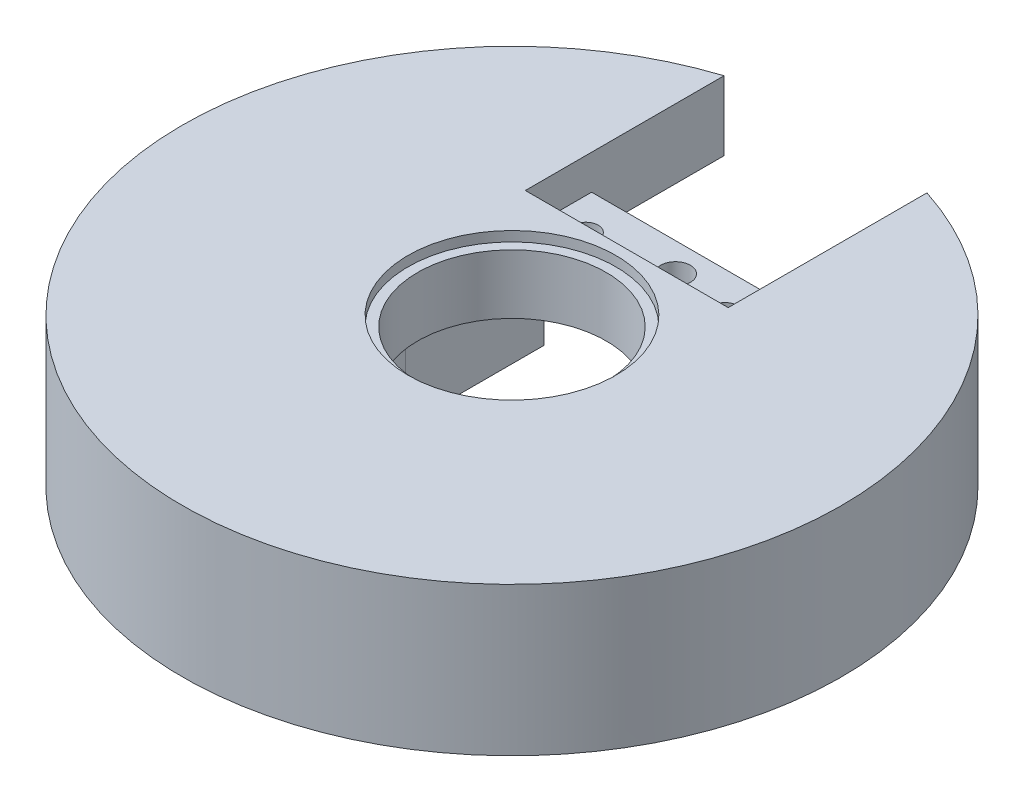
SolidWorks part; units mm, degrees
other "Markup2"
sketch "Sketch11" plane through (-33.3, 0, -31.6832) normal (-0.1985, -0.3048, -0.9315) x (0.9607, 0.1275, -0.2465)
ref_plane "Front Plane" through (0, 0, 0) normal (0, 0, 1) x (1, 0, 0)
ref_plane "Top Plane" through (0, 0, 0) normal (0, 1, 0) x (1, 0, 0)
ref_plane "Right Plane" through (0, 0, 0) normal (1, 0, 0) x (0, 0, -1)
sketch "Sketch1" plane through (0, 0, 0) normal (0, 1, 0) x (1, 0, 0)
  circle A0 centre (0, 0) radius 33.3
  dimension "D1" = 66.6
extrude "Boss-Extrude1" add sketch "Sketch1" along normal blind 15
sketch "Sketch3" plane through (0, 0, 0) normal (0, -1, 0) x (1, 0, 0)
  line L0 (3.2928, 18) -> (-5.3006, 18) construction
  line L1 (2.5019, 18) -> (-2.5019, 18)
  arc A0 (-2.5019, 18) -> (2.5019, 18) centre (0, 18) ccw
  point P10 (0, 0)
  dimension "D1" = 18
revolve "Cut-Revolve7" cut sketch "Sketch3" angle 360 about L0
pattern_circular "CirPattern1" count 3 over 360 about axis through (0, 0, 0) along (0, 1, 0) of "Cut-Revolve7"
sketch "Sketch5" plane through (0, 0, 0) normal (0, -1, 0) x (1, 0, 0)
  line L0 (-10.75, 0) -> (-10.75, -14)
  line L1 (-10.75, -14) -> (-21.8655, -25.1155)
  line L2 (0, -1.8595) -> (0, 3.43) construction
  line L3 (10.75, 0) -> (10.75, -14)
  line L4 (10.75, -14) -> (21.8655, -25.1155)
  circle A0 centre (0, 0) radius 10.75
  circle A3 centre (0, 0) radius 33.3 construction
  circle A4 centre (0, 0) radius 33.3
  circle M5 centre (0, 0) radius 33.3
  dimension "D1" = 21.5
  dimension "D2" = 14
  dimension "D3" = 135
extrude "Cut-Extrude1" cut sketch "Sketch5" against normal blind 8 contours A0 L0 L1 L4 L3 M5 | A0 region at (0, 0, -21.4079) region at (0, 0, 0)
sketch "Sketch6" plane through (0, 15, 0) normal (0, 1, 0) x (1, 0, 0)
  circle A0 centre (0, 0) radius 9.525
  circle A1 centre (0, 0) radius 10.5
  dimension "D1" = 19.05
  dimension "D2" = 21
extrude "Cut-Extrude3" cut sketch "Sketch6" against normal up to next contours A0 region at (0, 15, 0)
extrude "Cut-Extrude4" cut sketch "Sketch6<4>" against normal blind 1 contours A1 A0 region at (-10.203, 15, 0)
sketch "Sketch6<4>" plane through (0, 15, 0) normal (0, 1, 0) x (1, 0, 0) same geometry as "Sketch6"
sketch "Sketch7" plane through (0, 15, 0) normal (0, 1, 0) x (1, 0, 0)
  line L0 (-7.03, 14.5) -> (7.03, 14.5) construction
  circle A0 centre (-7.03, 14.5) radius 1.25
  circle A1 centre (7.03, 14.5) radius 1.25
  circle A2 centre (1.13, 15.4) radius 1.5
  point P4 (0, 14.5)
  dimension "D1" = 2.5
  dimension "D4" = 0.9
  dimension "3mm" = 3
  dimension "D2" = 14.06
  dimension "D3" = 14.5
  dimension "D5" = 5.9
extrude "Cut-Extrude5" cut sketch "Sketch7" against normal through all
sketch "Sketch8" plane through (0, 15, 0) normal (0, 1, 0) x (1, 0, 0)
  line L1 (-10.25, 11.6) -> (10.25, 11.6)
  line L2 (-10.25, 11.6) -> (-10.25, 36.6)
  line L3 (-10.25, 36.6) -> (10.25, 36.6)
  line L4 (10.25, 11.6) -> (10.25, 36.6)
  line L5 (-10.25, 11.6) -> (10.25, 36.6) construction
  line L6 (-10.25, 36.6) -> (10.25, 11.6) construction
  circle A0 centre (-7.03, 14.5) radius 1.25 construction
  point P0 (0, 24.1)
  point P7 (0, 0)
  dimension "D1" = 25
  dimension "D2" = 20.5
  dimension "D3" = 2.9
extrude "Cut-Extrude6" cut sketch "Sketch8" against normal blind 3.5
sketch "Sketch9" plane through (0, 11.5, 0) normal (0, 1, 0) x (1, 0, 0)
  line L0 (10.25, 11.6) -> (10.25, 31.6832) construction
  line L1 (-10.25, 18.3) -> (10.25, 18.3)
  line L2 (-10.25, 18.3) -> (-10.25, 38.3)
  line L3 (-10.25, 38.3) -> (10.25, 38.3)
  line L4 (10.25, 18.3) -> (10.25, 38.3)
  line L5 (-10.25, 18.3) -> (10.25, 38.3) construction
  line L6 (-10.25, 38.3) -> (10.25, 18.3) construction
  line L7 (-10.25, 31.6832) -> (-10.25, 11.6) construction
  circle A0 centre (-7.03, 14.5) radius 1.25 construction
  point P0 (0, 28.3)
  dimension "D1" = 3.8
  dimension "D2" = 20
extrude "Cut-Extrude7" cut sketch "Sketch9" against normal up to next
